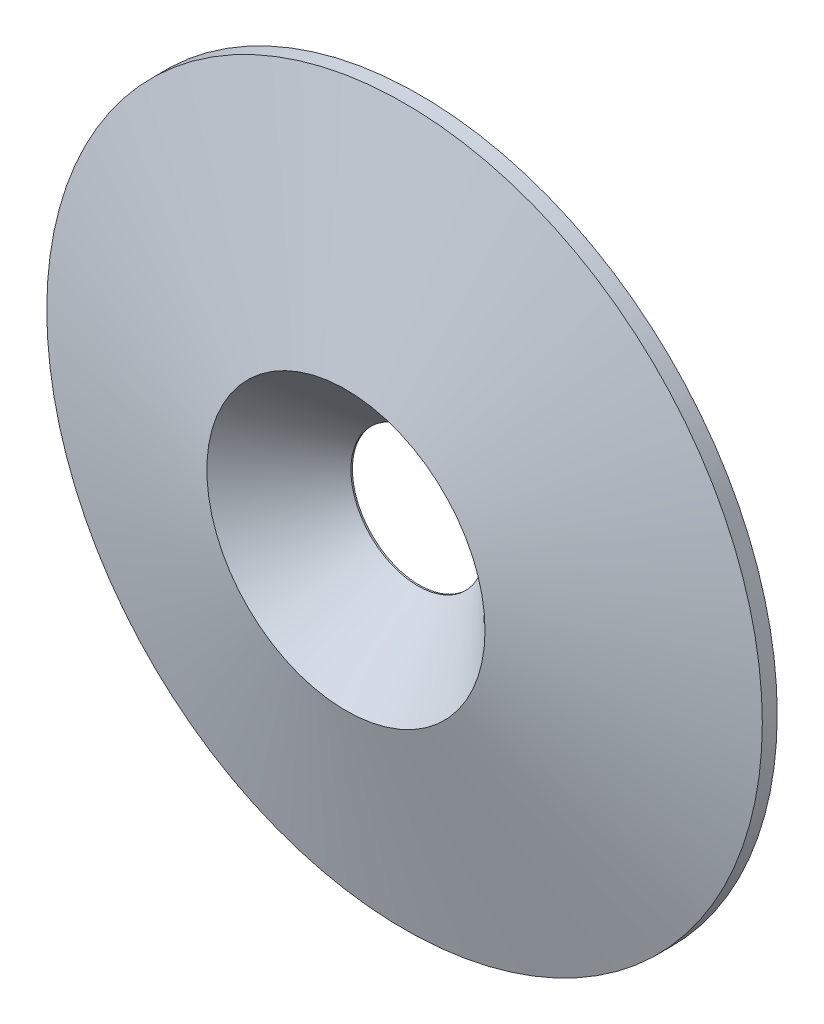
SolidWorks part; units mm, degrees
ref_plane "Front Plane" through (0, 0, 0) normal (0, 0, 1) x (1, 0, 0)
ref_plane "Top Plane" through (0, 0, 0) normal (0, 1, 0) x (1, 0, 0)
ref_plane "Right Plane" through (0, 0, 0) normal (1, 0, 0) x (0, 0, -1)
sketch "Sketch1" plane through (0, 0, 0) normal (0, 0, 1) x (1, 0, 0)
  circle A0 centre (0, 0) radius 12
  dimension "D1" = 24
extrude "Boss-Extrude1" add sketch "Sketch1" along normal blind 2.5
hole_wizard "CSK for M4 Flat Head Machine Screw1" positions "Sketch2" profile "Sketch3" countersink size "M4" standard "ANSI Metric" end condition through all
sketch "Sketch2" plane through (0, 0, 2.5) normal (0, 0, 1) x (1, 0, 0)
  point P0 (0, 0)
sketch "Sketch3" plane through (0, 0, 2.5) normal (1, 0, 0) x (0, -1, 0)
  line L0 (0, 0) -> (0, 2.5)
  line L1 (0, 2.5) -> (2.25, 2.5)
  line L2 (2.25, 2.5) -> (2.25, 2.45)
  line L3 (2.25, 2.45) -> (4.7, 0)
  line L5 (4.7, 0) -> (0, 0)
  line L6 (-2.25, 2.45) -> (-4.7, 0) construction
  line L11 (0, -6.35) -> (0, 107.95) construction
  dimension "Thru Hole Dia." = 4.5
  dimension "Thru Hole Depth" = 2.5
  dimension "Near C'Sink Dia." = 9.4
  dimension "Near C'Sink Angle" = 90
chamfer "Chamfer1" distance 2 angle 75 1 edges at (12, 0, 2.5) first distance on face at (12, 0, 2.5)
